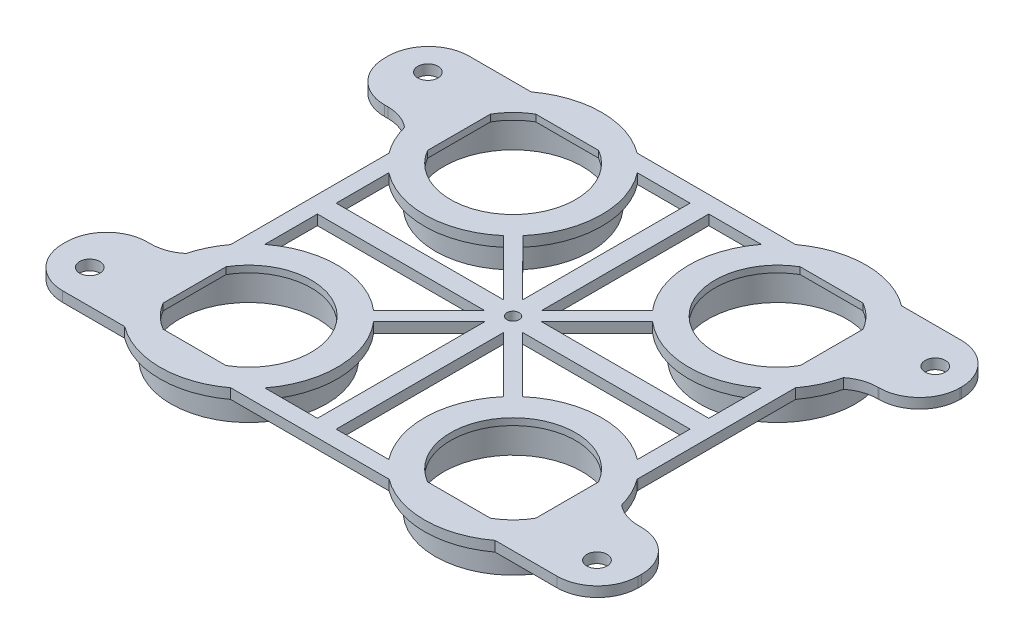
SolidWorks part; units mm, degrees
ref_plane "Front Plane" through (0, 0, 0) normal (0, 0, 1) x (1, 0, 0)
ref_plane "Top Plane" through (0, 0, 0) normal (0, 1, 0) x (1, 0, 0)
ref_plane "Right Plane" through (0, 0, 0) normal (1, 0, 0) x (0, 0, -1)
sketch "Sketch1" plane through (0, 0, 0) normal (0, 1, 0) x (1, 0, 0)
  line L1 (-55.1, 55.1) -> (55.1, 55.1)
  line L2 (-55.1, 55.1) -> (-55.1, -55.1)
  line L3 (-55.1, -55.1) -> (55.1, -55.1)
  line L4 (55.1, 55.1) -> (55.1, -55.1)
  line L5 (-55.1, 55.1) -> (55.1, -55.1) construction
  line L6 (-55.1, -55.1) -> (55.1, 55.1) construction
  line L7 (-60.1, 60.1) -> (60.1, 60.1)
  line L8 (-60.1, 60.1) -> (-60.1, -60.1)
  line L9 (-60.1, -60.1) -> (60.1, -60.1)
  line L10 (60.1, 60.1) -> (60.1, -60.1)
  line L11 (-60.1, 60.1) -> (60.1, -60.1) construction
  line L12 (-60.1, -60.1) -> (60.1, 60.1) construction
  point P0 (0, 0)
  point P6 (0, 0)
  dimension "D1" = 5
  dimension "D2" = 110.2
extrude "Boss-Extrude1" add sketch "Sketch1" along normal blind 3
sketch "Sketch3" plane through (0, 0, 0) normal (0, -1, 0) x (-1, 0, 0)
  line L0 (75.1, -50.1) -> (75.1, 49.9)
  line L1 (60.1, -60.1) -> (85.1, -60.1)
  line L2 (60.1, -60.1) -> (60.1, -35.1)
  line L3 (60.1, -35.1) -> (85.1, -35.1)
  line L4 (85.1, -60.1) -> (85.1, -35.1)
  line L5 (-60.1, -60.1) -> (-85.1, -60.1)
  line L6 (-60.1, -60.1) -> (-60.1, -35.1)
  line L7 (-60.1, -35.1) -> (-85.1, -35.1)
  line L8 (-85.1, -60.1) -> (-85.1, -35.1)
  line L9 (60.1, 60.1) -> (85.1, 60.1)
  line L10 (60.1, 60.1) -> (60.1, 35.1)
  line L11 (60.1, 35.1) -> (85.1, 35.1)
  line L12 (85.1, 60.1) -> (85.1, 35.1)
  line L13 (75.1, -50.1) -> (-74.9, -50.1)
  line L14 (60.1, -60.1) -> (-60.1, -60.1) construction
  line L15 (-60.1, 60.1) -> (-84.45, 60.1)
  line L16 (-60.1, 60.1) -> (-60.1, 35.75)
  line L17 (-60.1, 35.75) -> (-84.45, 35.75)
  line L18 (-84.45, 60.1) -> (-84.45, 35.75)
  circle A0 centre (75.1, -50.1) radius 3
  circle A1 centre (-74.9, -50.1) radius 3
  circle A2 centre (75.1, 49.9) radius 3
  circle A3 centre (-75.2602, 49.5981) radius 3
  line M15 (-60.1, 60.1) -> (-60.1, -60.1)
  line M17 (60.1, -60.1) -> (60.1, 60.1)
  dimension "D1" = 150
  dimension "D2" = 100
  dimension "D4" = 6
  dimension "D5" = 0
  dimension "D6" = 15
  dimension "D7" = 10
  dimension "D3" = 25
extrude "Boss-Extrude3" add sketch "Sketch3" against normal blind 3 contours A0 L13 L1 L4 L3 L0 M17 | A0 L0 L3 L2 L13 | A2 L11 L12 L9 M17 | A1 L7 L8 L5 L6 M15 | L15 L18 L17 A3 M15 region at (-67.398, 0, 42.398) region at (-75.4536, 0, 41.1) region at (72.1255, 0, -47.8412) region at (72.491, 0, 47.4815) region at (-72.4815, 0, -47.491)
fillet "Fillet1" radius 12 12 edges at (85.1, 1.5, 60.1) (85.1, 1.5, 35.1) (60.1, 1.5, 35.1) (-85.1, 1.5, -60.1) (-85.1, 1.5, -35.1) (-60.1, 1.5, -35.1) (-60.1, 1.5, 35.1) (-85.1, 1.5, 60.1) (-85.1, 1.5, 35.1) (84.45, 1.5, -60.1) (84.45, 1.5, -35.75) (60.1, 1.5, -35.75)
sketch "Sketch4" plane through (0, 0, 0) normal (0, -1, 0) x (-1, 0, 0)
  line L1 (55.1, -55.1) -> (39.1, -55.1) construction
  line L2 (55.1, -55.1) -> (55.1, -39.1) construction
  line L3 (55.1, -39.1) -> (39.1, -39.1) construction
  line L4 (39.1, -55.1) -> (39.1, -39.1) construction
  circle A0 centre (39.1, -39.1) radius 18.5
  circle A1 centre (39.1, -39.1) radius 26.2037
  dimension "D1" = 16
extrude "Boss-Extrude4" add sketch "Sketch4" against normal blind 3
sketch "Sketch5" plane through (0, 0, 0) normal (0, -1, 0) x (-1, 0, 0)
  circle A0 centre (39.1, -39.1) radius 20.5
  circle A1 centre (39.1, -39.1) radius 23
extrude "Boss-Extrude5" add sketch "Sketch5" along normal blind 8
sketch "Sketch6" plane through (0, 0, 0) normal (0, 1, 0) x (1, 0, 0)
  circle A0 centre (0, 0) radius 14.2988
extrude "Boss-Extrude6" add sketch "Sketch6" along normal blind 5.7 separate body
pattern_circular "CirPattern1" count 4 over 360 about axis through (0, 0, 0) along (0, 1, 0) of "Boss-Extrude4", "Boss-Extrude5"
sketch "Sketch7" plane through (0, 0, 0) normal (0, -1, 0) x (-1, 0, 0)
  circle A0 centre (0, 0) radius 21.6867
extrude "Cut-Extrude1" cut sketch "Sketch7" against normal blind 5.7
sketch "Sketch8" plane through (0, 0, 0) normal (0, -1, 0) x (-1, 0, 0)
  line L0 (-55.1, -18.3483) -> (-55.1, 18.3483) construction
  line L1 (55.1, -2.7739) -> (-55.1, -2.7739)
  line L2 (55.1, -2.7739) -> (55.1, 2.7739)
  line L3 (55.1, 2.7739) -> (-55.1, 2.7739)
  line L4 (-55.1, -2.7739) -> (-55.1, 2.7739)
  line L5 (55.1, -2.7739) -> (-55.1, 2.7739) construction
  line L6 (55.1, 2.7739) -> (-55.1, -2.7739) construction
  line L8 (-2.7739, -58.5995) -> (2.7739, -58.5995)
  line L9 (-2.7739, -58.5995) -> (-2.7739, 58.5995)
  line L10 (-2.7739, 58.5995) -> (2.7739, 58.5995)
  line L11 (2.7739, -58.5995) -> (2.7739, 58.5995)
  line L12 (-2.7739, -58.5995) -> (2.7739, 58.5995) construction
  line L13 (-2.7739, 58.5995) -> (2.7739, -58.5995) construction
  point P0 (0, 0)
  point P8 (0, 0)
extrude "Boss-Extrude7" add sketch "Sketch8" against normal blind 3 contours L8 L11 L1 L9 | L1 L9 L3 L4 | L1 L11 L3 L9 | L11 L1 L2 L3 | L3 L11 L10 L9 region at (-28.937, 0, 0) region at (0, 0, 30.6867) region at (0, 0, 0) region at (28.937, 0, 0) region at (0, 0, -30.6867)
sketch "Sketch9" plane through (0, 0, 0) normal (0, -1, 0) x (-1, 0, 0)
  line L0 (22.8242, 20.0348) -> (-19.9932, -22.8607)
  line L1 (22.8242, 20.0348) -> (19.9932, 22.8607)
  line L2 (-19.9932, -22.8607) -> (-22.8242, -20.0348)
  line L3 (19.9932, 22.8607) -> (-22.8242, -20.0348)
  line L4 (-21.4087, -21.4477) -> (21.4087, 21.4477) construction
  line L5 (1.4155, -1.4129) -> (-1.4155, 1.4129) construction
  point P1 (0, 0)
extrude "Boss-Extrude8" add sketch "Sketch9" against normal blind 3
sketch "Sketch10" plane through (0, 0, 0) normal (0, -1, 0) x (-1, 0, 0)
  line L0 (23.3841, -20.5545) -> (-20.5558, 23.383)
  line L1 (23.3841, -20.5545) -> (20.5558, -23.383)
  line L2 (-20.5558, 23.383) -> (-23.3841, 20.5545)
  line L3 (20.5558, -23.383) -> (-23.3841, 20.5545)
  line L4 (-21.9699, 21.9688) -> (21.9699, -21.9688) construction
  line L5 (1.4142, 1.4143) -> (-1.4142, -1.4143) construction
  point P0 (-21.1514, 21.1502)
  point P1 (0, 0)
extrude "Boss-Extrude9" add sketch "Sketch10" against normal blind 3
sketch "Sketch12" plane through (0, -8, 0) normal (0, -1, 0) x (-1, 0, 0)
  circle A0 centre (39.1, -39.1) radius 20.5
extrude "Cut-Extrude2" cut sketch "Sketch12" against normal blind 9
sketch "Sketch13" plane through (0, 0, 0) normal (0, -1, 0) x (-1, 0, 0)
  circle A0 centre (0, 0) radius 3.7471
sketch "Sketch14" plane through (0, 0, 0) normal (0, -1, 0) x (-1, 0, 0)
  circle A0 centre (0, 0) radius 1.8125
extrude "Cut-Extrude3" cut sketch "Sketch14" against normal blind 9
pattern_circular "CirPattern2" count 4 over 360 about axis through (0, 0, 0) along (0, -1, 0) of "Cut-Extrude2"
